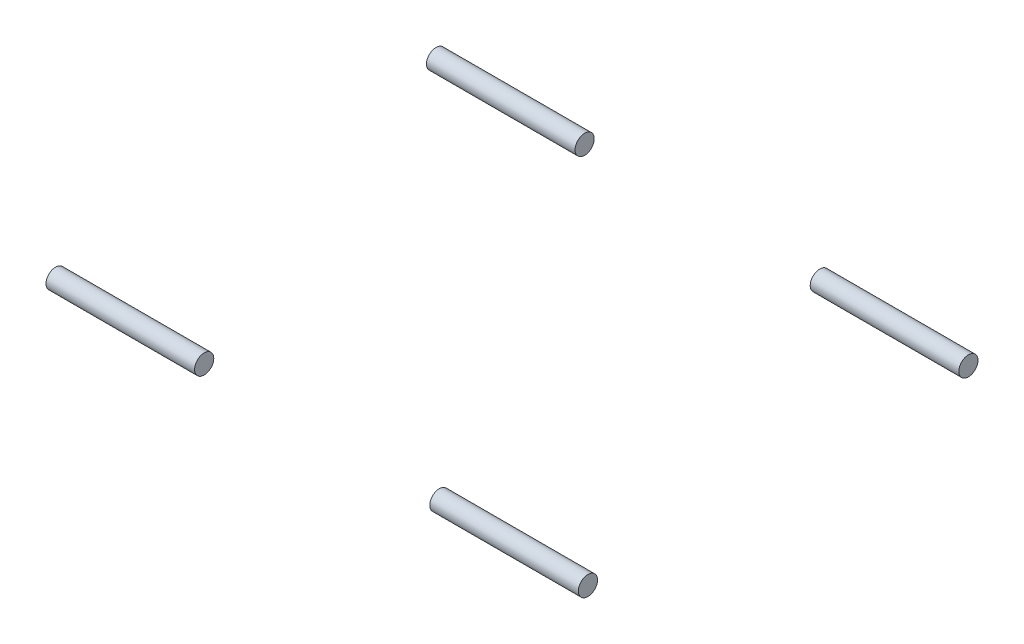
SolidWorks part; units mm, degrees
material "6061-T6 (SS)"
ref_plane "Front Plane" through (0, 0, 0) normal (0, 0, 1) x (1, 0, 0)
ref_plane "Top Plane" through (0, 0, 0) normal (0, 1, 0) x (1, 0, 0)
ref_plane "Right Plane" through (0, 0, 0) normal (1, 0, 0) x (0, 0, -1)
sketch "Sketch1" plane through (88.15, 0, 0) normal (-1, 0, 0) x (0, 0, 1)
  circle A0 centre (126, 0) radius 3.175
  circle A1 centre (0, 0) radius 3.175
  circle A2 centre (0, 0) radius 3.175 construction
  circle A3 centre (126, 0) radius 3.175 construction
extrude "Boss-Extrude1" add sketch "Sketch1" along normal up to surface (49.2125 mm away)
mirror "Mirror1" about plane through (0, 0, 0) normal (1, 0, 0) of bodies 101 102
